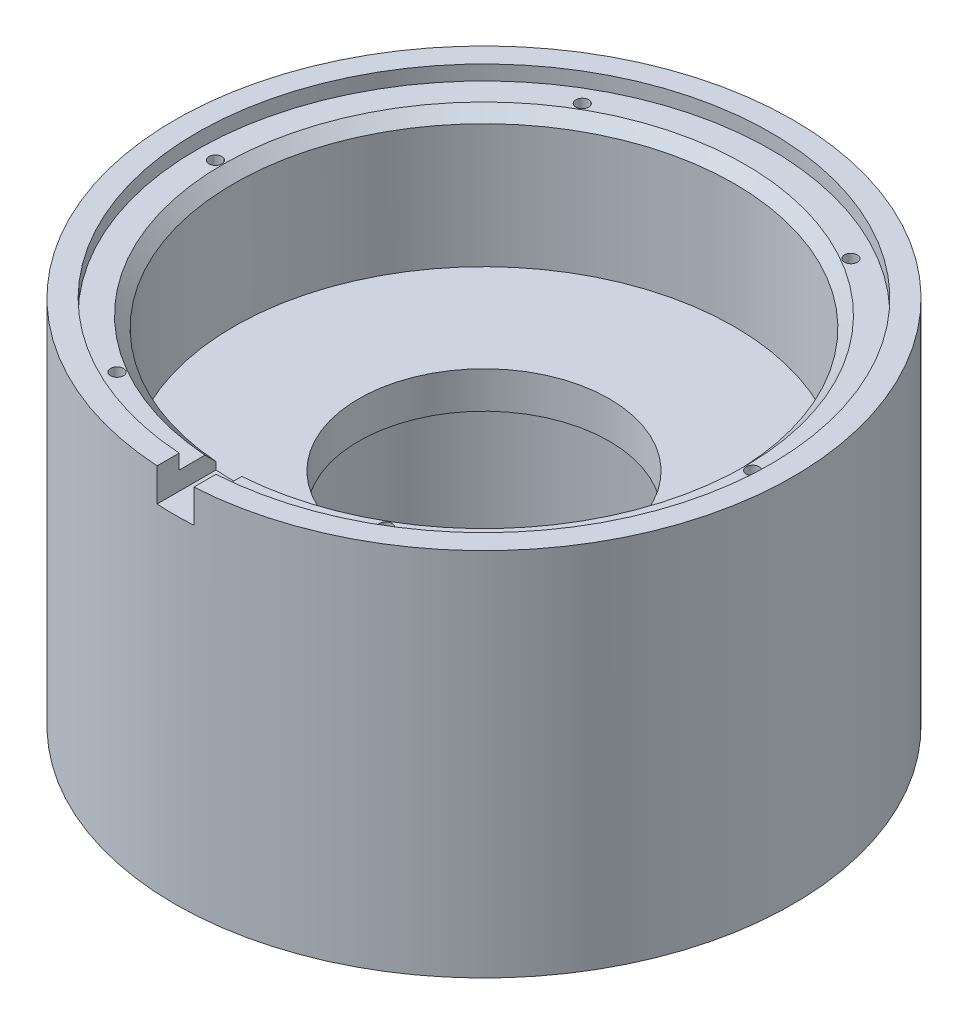
SolidWorks part; units mm, degrees
ref_plane "Front Plane" through (0, 0, 0) normal (0, 0, 1) x (1, 0, 0)
ref_plane "Top Plane" through (0, 0, 0) normal (0, 1, 0) x (1, 0, 0)
ref_plane "Right Plane" through (0, 0, 0) normal (1, 0, 0) x (0, 0, -1)
sketch "Sketch7" plane through (0, 0, 0) normal (0, 0, 1) x (1, 0, 0)
  line L0 (0, -30.2319) -> (0, 30.2319) construction
  line L1 (-42.0375, 22.84) -> (-39.0375, 22.84)
  line L2 (-39.0375, 22.84) -> (-39.0375, 20.84)
  line L3 (-39.0375, 20.84) -> (-34.0375, 20.84)
  line L4 (-34.0375, 20.84) -> (-34.0375, 2.5)
  line L5 (-25, -2.5) -> (-17.0375, -2.5)
  line L6 (-17.0375, -2.5) -> (-17.0375, 2.5)
  line L7 (-17.0375, 2.5) -> (-34.0375, 2.5)
  line L8 (-25, -2.5) -> (-25, -27.5)
  line L9 (-25, -27.5) -> (-42.0375, -27.5)
  line L10 (-42.0375, -27.5) -> (-42.0375, 22.84)
  line L11 (-17.0375, 0) -> (0, 0) construction
  point P4 (0, 0)
  point P12 (-20.6843, 2.5)
  point P18 (0, 0)
  point P19 (-34.1247, -17.4996)
  point P20 (-36.5375, 20.84)
  dimension "D1" = 3
  dimension "D2" = 2
  dimension "D3" = 5
  dimension "D4" = 34.0375
  dimension "D7" = 5
  dimension "D8" = 17
  dimension "D6" = 25
  dimension "D9" = 25
  dimension "D5" = 18.34
revolve "Base Motor Housing" add sketch "Sketch7" angle 360 about L0
sketch "Sketch8" plane through (0, 22.84, 0) normal (0, 1, 0) x (1, 0, 0)
  line L0 (0, 0) -> (0, -42.0375) construction
  line L1 (-2.5, -42.0375) -> (2.5, -42.0375)
  line L2 (-2.5, -42.0375) -> (-2.5, -33.9456)
  line L3 (-2.5, -33.9456) -> (2.5, -33.9456)
  line L4 (2.5, -42.0375) -> (2.5, -33.9456)
  circle A0 centre (0, 0) radius 42.0375 construction
  circle A1 centre (0, 0) radius 34.0375 construction
  point P10 (0, -42.0375)
  point P11 (0, 0)
  dimension "D1" = 5
extrude "Wire Hole" cut sketch "Sketch8" against normal offset from surface (4.5 mm away) 2.5 up to face at (0, 20.84, -39.0375)
sketch "Sketch9" plane through (0, 20.84, 0) normal (0, 1, 0) x (1, 0, 0)
  circle A0 centre (0, 0) radius 34.0375 construction
  circle A1 centre (0, 0) radius 34.0375 construction
  circle A2 centre (0, 0) radius 36.5375 construction
  circle A3 centre (-36.5375, 0) radius 0.875
  circle A4 centre (-18.2687, 31.6424) radius 0.875
  circle A5 centre (18.2688, 31.6424) radius 0.875
  circle A6 centre (36.5375, 0) radius 0.875
  circle A7 centre (18.2687, -31.6424) radius 0.875
  circle A8 centre (-18.2688, -31.6424) radius 0.875
  point P9 (0, 0)
  point P10 (0, 0)
  point P21 (0, 0)
  dimension "D2" = 1.75
  dimension "D1" = 2.5
  dimension "D3" = 6
extrude "Cut-Extrude4" cut sketch "Sketch9" against normal blind 6
sketch "Sketch10" plane through (0, -27.5, 0) normal (0, -1, 0) x (1, 0, 0)
  line L0 (-25, 0) -> (-42.0375, 0) construction
  circle A0 centre (0, 0) radius 25 construction
  circle A1 centre (0, 0) radius 25 construction
  circle A2 centre (0, 0) radius 42.0375 construction
  circle A3 centre (0, 0) radius 42.0375 construction
  circle A4 centre (-33.5187, 0) radius 2.875
  circle A5 centre (-16.7594, 29.0281) radius 2.875
  circle A6 centre (16.7594, 29.0281) radius 2.875
  circle A7 centre (33.5187, 0) radius 2.875
  circle A8 centre (16.7594, -29.0281) radius 2.875
  circle A9 centre (-16.7594, -29.0281) radius 2.875
  circle A10 centre (0, 0) radius 33.5187 construction
  point P12 (0, 0)
  point P22 (0, 0)
  point P23 (0, 0)
  dimension "D1" = 5.75
  dimension "D2" = 6
extrude "Cut-Extrude5" cut sketch "Sketch10" against normal blind 20
chamfer "Chamfer1" distance 1.5 angle 45 1 edges at (0, 20.84, -34.0375)
equation "\"D2@Sketch9\"=\"Back_mount_hole\""
equation "\"Stator_OD\"= 68'No Tolerance given"
equation "\"D4@Sketch7\"= 1 / 2 * \"Stator_OD\" + \"Stator_Gap\""
equation "\"A\"=18.34"
equation "\"Rotor_ID\"= 34'No Tolerance Given"
equation "\"bearing_Thickness\"= 20'Currently non-sense"
equation "\"D8@Sketch7\"=1/2*(\"Stator_OD\"-\"Rotor_ID\")"
equation "\"D6@Sketch7\"=\"bearing_Thickness\"+5"
equation "\"bearing_OD\"= 50'currently non-sense"
equation "\"D9@Sketch7\"=\"bearing_OD\"*1/2"
equation "\"D5@Sketch7\"=\"A\""
equation "\"Stator_Gap\"= 0.0375'+- 0.0125 (From 1.3.3.1 Kollmorgen manual)"
equation "\"Back_mount_hole\"= 1.75'To be tapped to M2 (USE LOCKTITE)"
equation "\"D1@Cut-Extrude5\"=\"bearing_Thickness\""
equation "\"facePlate_Mount_Hole\"= 5.75'To be tapped to M6"
equation "\"D1@Sketch10\"=\"facePlate_Mount_Hole\""
